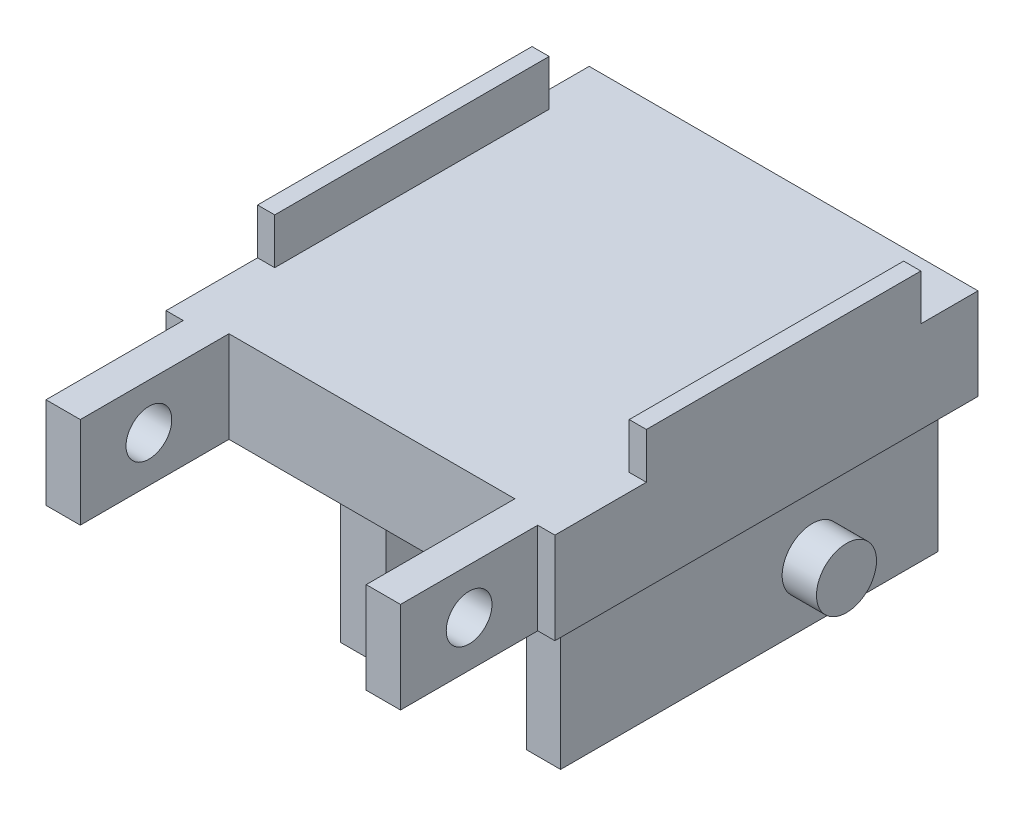
SolidWorks part; units mm, degrees
ref_plane "前视基准面" through (0, 0, 0) normal (0, 0, 1) x (1, 0, 0)
ref_plane "上视基准面" through (0, 0, 0) normal (0, 1, 0) x (1, 0, 0)
ref_plane "右视基准面" through (0, 0, 0) normal (1, 0, 0) x (0, 0, -1)
sketch "草图1" plane through (0, 0, 0) normal (0, 1, 0) x (1, 0, 0)
  line L1 (17, -24.5) -> (-17, -24.5)
  line L2 (17, -24.5) -> (17, 24.5)
  line L3 (17, 24.5) -> (-17, 24.5)
  line L4 (-17, -24.5) -> (-17, 24.5)
  line L5 (0, 24.5) -> (0, -24.5) construction
  line L6 (17, 0) -> (-17, 0) construction
  point P0 (0, 0)
  dimension "D1" = 49
  dimension "D2" = 34
extrude "凸台-拉伸1" add sketch "草图1" along normal blind 8
sketch "草图2" plane through (0, 8, 0) normal (0, 1, 0) x (1, 0, 0)
  line L0 (-17, 24.5) -> (-17, -24.5) construction
  line L1 (-17, 19.5) -> (-15.5, 19.5)
  line L2 (-17, 19.5) -> (-17, -4.5)
  line L3 (-17, -4.5) -> (-15.5, -4.5)
  line L4 (-15.5, 19.5) -> (-15.5, -4.5)
  line L5 (17, 24.5) -> (-17, 24.5) construction
  line L6 (0, -55) -> (0, 55) construction
  line L7 (17, -4.5) -> (15.5, -4.5)
  line L8 (15.5, 19.5) -> (15.5, -4.5)
  line L9 (17, 19.5) -> (17, -4.5)
  line L10 (17, 19.5) -> (15.5, 19.5)
  dimension "D1" = 1.5
  dimension "D2" = 24
  dimension "D3" = 5
extrude "凸台-拉伸2" add sketch "草图2" along normal blind 4
sketch "草图3" plane through (0, 8, 0) normal (0, 1, 0) x (1, 0, 0)
  line L0 (-17, -24.5) -> (17, -24.5) construction
  line L1 (-17, -24.5) -> (-15.5, -24.5)
  line L2 (-17, -24.5) -> (-17, -12.5)
  line L3 (-17, -12.5) -> (-15.5, -12.5)
  line L4 (-15.5, -24.5) -> (-15.5, -12.5)
  line L5 (17, -24.5) -> (15.5, -24.5)
  line L6 (17, -24.5) -> (17, -12.5)
  line L7 (17, -12.5) -> (15.5, -12.5)
  line L8 (15.5, -24.5) -> (15.5, -12.5)
  line L10 (-12.5, -24.5) -> (12.5, -24.5)
  line L11 (-12.5, -24.5) -> (-12.5, -11.5)
  line L12 (-12.5, -11.5) -> (12.5, -11.5)
  line L13 (12.5, -24.5) -> (12.5, -11.5)
  dimension "D1" = 1.5
  dimension "D2" = 1.5
  dimension "D3" = 12
  dimension "D4" = 12
  dimension "D5" = 13
  dimension "D6" = 3
  dimension "D7" = 3
extrude "切除-拉伸1" cut sketch "草图3" against normal up to surface (8 mm away) up to face at (0, 0, 0)
sketch "草图4" plane through (-15.5, 0, 0) normal (-1, 0, 0) x (0, 0, 1)
  line L0 (24.5, 0) -> (24.5, 8) construction
  line L1 (24.5, 8) -> (12.5, 8) construction
  circle A0 centre (18.5, 4) radius 2
  dimension "D1" = 6
  dimension "D2" = 4
  dimension "D3" = 4
extrude "切除-拉伸2" cut sketch "草图4" against normal up to surface (31 mm away) up to face at (15.5, 4, 18.5)
sketch "草图5" plane through (0, 0, 0) normal (0, -1, 0) x (1, 0, 0)
  line L0 (-12.5, 11.5) -> (12.5, 11.5) construction
  line L1 (4, 11.5) -> (-4, 11.5)
  line L2 (4, 11.5) -> (4, 41.5)
  line L4 (-4, 11.5) -> (-4, 41.5)
  line L5 (13, 41.5) -> (4, 41.5)
  line L7 (13, 41.5) -> (13, 56.5)
  line L8 (13, 56.5) -> (-13, 56.5)
  line L9 (-13, 41.5) -> (-13, 56.5)
  line L10 (-4, 41.5) -> (-13, 41.5)
  point P6 (0, 11.5)
  dimension "D1" = 8
  dimension "D2" = 30
  dimension "D3" = 26
  dimension "D4" = 15
  dimension "D5" = 9
extrude "凸台-拉伸3" add sketch "草图5" against normal blind 8
extrude "切除-拉伸4" cut sketch "草图5<2>" against normal up to surface (8 mm away) up to face at (0, 8, 13)
sketch "草图5<2>" plane through (0, 0, 0) normal (0, -1, 0) x (1, 0, 0) same geometry as "草图5"
sketch "草图6" plane through (0, 0, 0) normal (0, -1, 0) x (1, 0, 0)
  line L0 (-17, -24.5) -> (-17, 12.5) construction
  line L2 (-17, 12.5) -> (-17, 1.1778)
  line L5 (-17, -24.5) -> (-17, 10.5)
  line L11 (-15, 10) -> (-4.25, 10)
  line L20 (-4.25, 10) -> (-4.25, 6)
  line L22 (-4.25, 6) -> (-0.25, 6)
  line L25 (-4.25, -19.5) -> (-4.25, -19)
  line L28 (-0.25, 6) -> (-0.25, 10)
  line L29 (-4.25, 10) -> (-0.25, 10)
  line L30 (-4.25, -19) -> (0, -19)
  line L31 (-4.25, -23) -> (-4.25, -19.5)
  line L32 (-15, 10) -> (-15, -23)
  line L33 (15, 10) -> (15, -23)
  line L35 (0, -19.5) -> (0, -23)
  line L36 (-15, 10) -> (12, 10)
  line L37 (12, 10) -> (15, 10)
  line L39 (12, -23) -> (15, -23)
  line L40 (-4.25, -23) -> (0, -23)
  line L41 (0, -19) -> (0, -19.5)
  line L42 (12, 10) -> (12, -23)
extrude "凸台-拉伸5" add sketch "草图6" along normal blind 12 contours L29 L20 L22 L28 | L42 L39 L33 L37 | L31 L40 L35 region at (-2.25, 0, 8) region at (13.5, 0, -6.5) region at (-2.125, 0, -21)
sketch "草图7" plane through (15, 0, 0) normal (1, 0, 0) x (0, 0, -1)
  line L0 (23, -12) -> (12, -12)
  line L1 (-10, -12) -> (23, -12) construction
  line L2 (12, -12) -> (12, -7)
  circle A0 centre (12, -7) radius 2.625
extrude "凸台-拉伸6" add sketch "草图7" along normal blind 3 contours A0
sketch "草图8" plane through (-4.25, 0, 0) normal (-1, 0, 0) x (0, 0, 1)
  line L0 (8, -12) -> (8, -7)
  line L1 (10, -12) -> (6, -12) construction
  line L3 (-23, -12) -> (-19, -12) construction
  line L4 (-21, -12) -> (-21, -7)
  circle A0 centre (8, -7) radius 0.55
  circle A1 centre (-21, -7) radius 0.55
extrude "切除-拉伸5" cut sketch "草图8" against normal blind 4 contours A0 | A1
